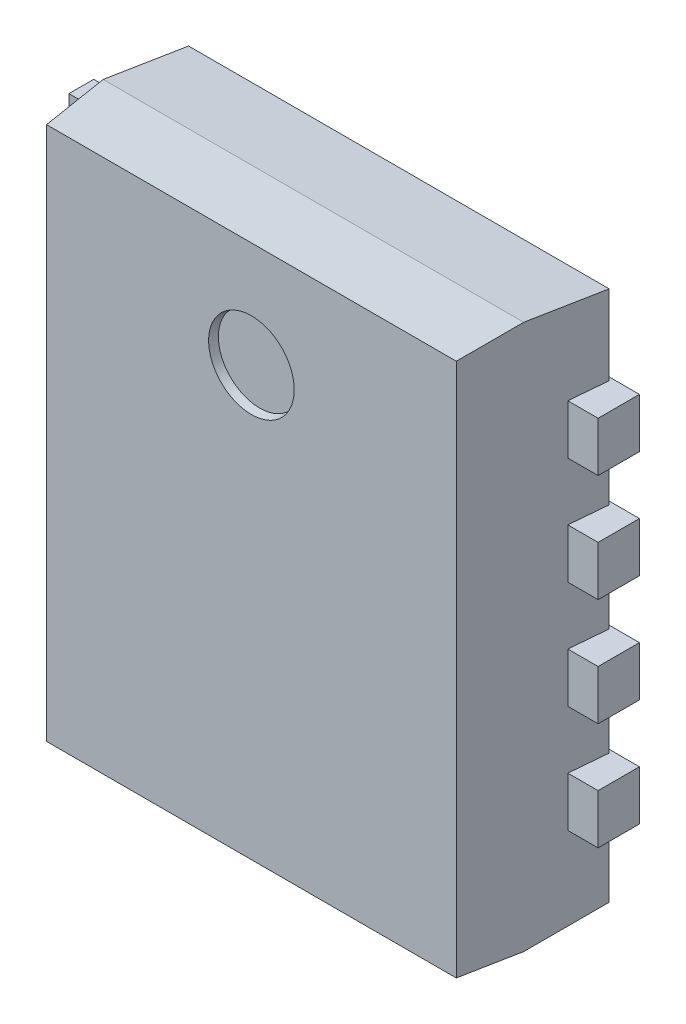
SolidWorks part; units mm, degrees
ref_plane "Front Plane" through (0, 0, 0) normal (0, 0, 1) x (1, 0, 0)
ref_plane "Top Plane" through (0, 0, 0) normal (0, 1, 0) x (1, 0, 0)
ref_plane "Right Plane" through (0, 0, 0) normal (1, 0, 0) x (0, 0, -1)
sketch "Sketch2" plane through (0, 0, 0) normal (0, 0, 1) x (1, 0, 0)
  line L0 (1.15, 0.175) -> (1.15, -0.175)
  line L1 (-0.475, 1.125) -> (1.65, 1.125)
  line L2 (-0.475, 1.125) -> (-0.475, -1.125)
  line L3 (-0.475, -1.125) -> (1.65, -1.125)
  line L4 (1.15, 0.825) -> (1.15, 0.475)
  line L7 (1.15, 0.825) -> (1.65, 0.825)
  line L8 (1.65, 1.125) -> (1.65, 0.825)
  line L9 (1.15, 0.475) -> (1.65, 0.475)
  line L11 (1.15, 0.175) -> (1.65, 0.175)
  line L12 (1.65, 0.475) -> (1.65, 0.175)
  line L13 (1.15, -0.175) -> (1.65, -0.175)
  line L15 (1.15, -0.475) -> (1.65, -0.475)
  line L16 (1.65, -0.175) -> (1.65, -0.475)
  line L19 (1.15, -0.825) -> (1.65, -0.825)
  line L20 (1.65, -1.125) -> (1.65, -0.825)
  line L21 (1.15, -0.475) -> (1.15, -0.825)
  line L22 (2.2725, 0) -> (-1.4578, 0) construction
  point P1 (-0.1958, 0)
  point P3 (2.7611, -1.1125)
  point P21 (-0.475, 0)
  point P22 (0, 0)
  point P23 (0, 0)
  point P24 (2.5054, 1.1125)
  point P25 (2.6551, 1.1125)
  point P26 (-1.2289, 0)
  point P27 (2.2725, 0)
  point P28 (-1.4578, 0)
  dimension "D1" = 0.3
  dimension "D2" = 2.25
  dimension "D3" = 2.125
  dimension "D4" = 0.5
  dimension "D5" = 1.65
extrude "Boss-Extrude1" add sketch "Sketch2" along normal blind 0.25
fillet "Fillet1" radius 0.1 8 edges at (1.15, 0.175, 0.125) (1.15, -0.825, 0.125) (1.15, -0.475, 0.125) (1.15, -0.175, 0.125) (1.15, 0.475, 0.125) (1.15, 0.825, 0.125) (-0.475, 1.125, 0.125) (-0.475, -1.125, 0.125)
ref_plane "Plane1" through (0, 0, 0.02) normal (0, 0, 1) x (1, 0, 0)
sketch "Sketch3" plane through (0, 0, 0.02) normal (0, 0, 1) x (1, 0, 0)
  line L1 (-1.1, 1.65) -> (1.5, 1.65)
  line L2 (-1.1, 1.65) -> (-1.1, -1.65)
  line L3 (-1.1, -1.65) -> (1.5, -1.65)
  line L4 (1.5, 1.65) -> (1.5, -1.65)
  point P4 (-1.1, 0)
  dimension "D1" = 3.3
  dimension "D2" = 2.6
  dimension "D3" = 1.1
extrude "Boss-Extrude2" add sketch "Sketch3" along normal blind 0.85
chamfer "Chamfer2" distance 1 angle 5 1 edges at (1.5, 0, 0.87) first distance on face at (1.5, 0, 0.197)
chamfer "Chamfer3" distance 0.4 angle 5 3 edges at (0.1563, 1.65, 0.87) (0.1563, -1.65, 0.87) (-1.1, 0, 0.87) first distance on face at (0.1748, 1.65, 0.445) first distance on face at (0.1748, -1.65, 0.445) first distance on face at (-1.1, 0, 0.445)
chamfer "Chamfer4" distance 0.5 angle 5 3 edges at (0.1934, 1.65, 0.02) (-1.1, 0, 0.02) (0.1934, -1.65, 0.02) first distance on face at (0.1836, 1.65, 0.245) first distance on face at (-1.1, 0, 0.245) first distance on face at (0.1836, -1.65, 0.245)
ref_plane "Plane2" through (0, 0.975, 0) normal (0, 1, 0) x (1, 0, 0)
sketch "Sketch4" plane through (0, 0.975, 0) normal (0, 1, 0) x (1, 0, 0)
  line L0 (-1.65, 0) -> (-1.25, 0)
  line L1 (-1.25, 0) -> (-1.15, -0.5)
  line L2 (-1.15, -0.5) -> (-0.8498, -0.5)
  line L3 (-0.8498, -0.5) -> (-0.8498, -0.65)
  line L4 (-0.8498, -0.65) -> (-1.273, -0.65)
  line L5 (-1.273, -0.65) -> (-1.373, -0.15)
  line L6 (-1.373, -0.15) -> (-1.65, -0.15)
  line L7 (-1.65, -0.15) -> (-1.65, 0)
  point P3 (-1.118, -0.595)
  point P10 (-1.118, -0.595)
  point P11 (0, 0)
  point P12 (-1.1142, -0.6)
  dimension "D1" = 0.15
  dimension "D2" = 0.15
  dimension "D3" = 0.5
  dimension "D4" = 1.65
  dimension "D5" = 0.4
  dimension "D6" = 0.1
extrude "Boss-Extrude3" add sketch "Sketch4" along normal mid plane 0.3
fillet "Fillet2" radius 0.1 2 edges at (-1.373, 0.975, 0.15) (-1.15, 0.975, 0.5)
fillet "Fillet3" radius 0.2 2 edges at (-1.25, 0.975, 0) (-1.273, 0.975, 0.65)
pattern_linear "LPattern1" count 4 spacing 0.65 along (0, -1, 0) of "Boss-Extrude3", "Fillet2", "Fillet3"
sketch "Sketch5" plane through (0, 0, 0.87) normal (0, 0, 1) x (1, 0, 0)
  line L1 (0.4785, 0.975) -> (-0.4785, 0.975) construction
  line L2 (1.4125, 1.615) -> (-1.065, 1.615) construction
  circle A0 centre (0.1738, 0.975) radius 0.25
  point P4 (0.1835, 0.975)
  point P5 (0, 0)
  point P8 (0.1738, 1.615)
extrude "Cut-Extrude1" cut sketch "Sketch5" against normal blind 0.05
chamfer "Chamfer5" distance 0.05 angle 10 1 edges at (0.4238, 0.975, 0.87) first distance on face at (0.4238, 0.975, 0.82)
